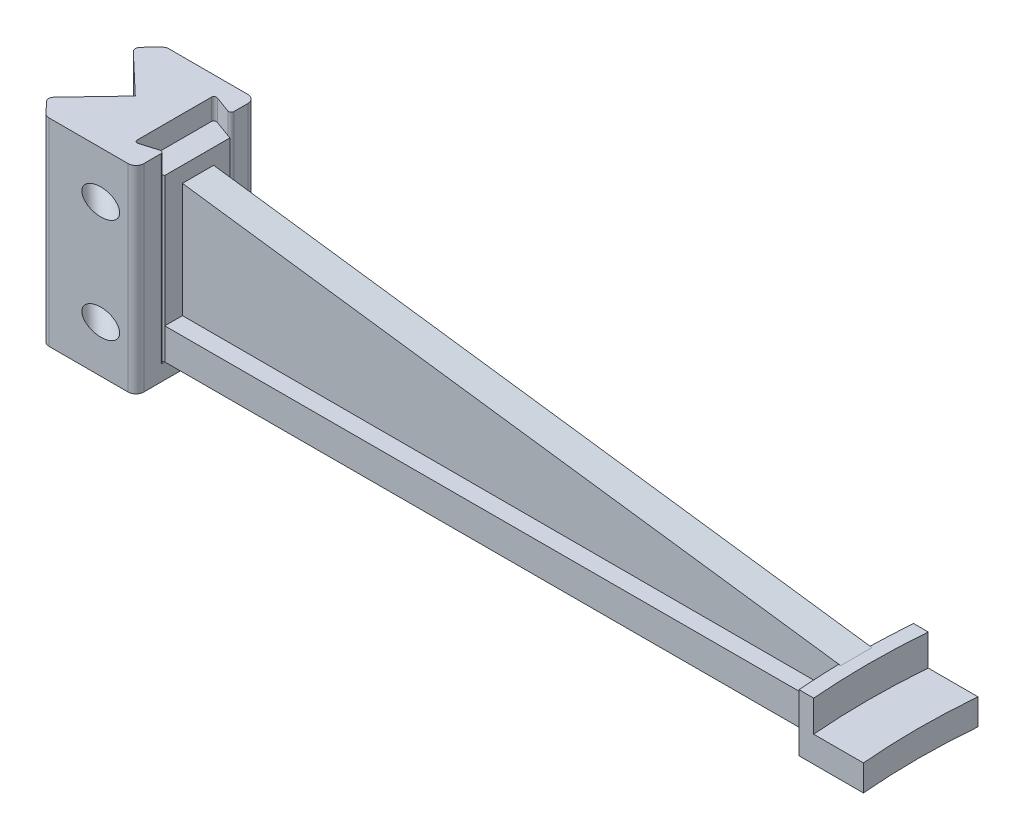
SolidWorks part; units mm, degrees
ref_plane "Front Plane" through (0, 0, 0) normal (0, 0, 1) x (1, 0, 0)
ref_plane "Top Plane" through (0, 0, 0) normal (0, 1, 0) x (1, 0, 0)
ref_plane "Right Plane" through (0, 0, 0) normal (1, 0, 0) x (0, 0, -1)
sketch "Sketch2" plane through (0, 0, 0) normal (0, 1, 0) x (1, 0, 0)
  line L0 (0, 0) -> (-276.0246, 0) construction
  line L1 (0, 0) -> (135.9511, 0) construction
  line L2 (-276.0246, 0) -> (-292.5966, 15.7434)
  line L3 (-292.5966, 15.7434) -> (-286.5108, 22.1496)
  line L4 (-286.5108, 22.1496) -> (-276.0246, 12.1877)
  line L5 (-276.0246, 12.1877) -> (-276.0246, 0)
  line L14 (0.8795, 22) -> (25.6062, 22)
  line L15 (0.8795, -22) -> (25.6062, -22)
  line L16 (25.6062, 22) -> (25.6062, -22) construction
  line L34 (-276.0246, 0) -> (-292.5966, -17.4443)
  line L49 (-292.5966, -17.4443) -> (-286.5108, -23.8504)
  line L50 (-286.5108, -23.8504) -> (-276.0246, -12.8123)
  line L51 (-276.0246, -12.8123) -> (-276.0246, 0)
  line L52 (-276.0246, 12.1877) -> (0.2836, 12.5)
  line L53 (-276.0246, -12.8123) -> (0.2836, -12.5)
  line L54 (0.2836, -12.5) -> (0.2836, 12.5) construction
  line L55 (-276.0246, 12.1877) -> (-276.0246, 24.2548) construction
  line L56 (-276.0246, -12.8123) -> (-276.0246, -19.1381)
  line L57 (-251.9246, 12.2149) -> (-260.9246, 15.4907)
  line L58 (-251.9246, 12.2149) -> (-251.9246, 22.1496)
  line L59 (-260.9246, 15.4907) -> (-260.9246, -15.4907)
  line L60 (-260.9246, -15.4907) -> (-251.9246, -12.7851)
  line L61 (-251.9246, -12.7851) -> (-251.9246, 12.2149)
  line L62 (-251.9246, 12.3214) -> (-261.0246, 15.6335)
  line L63 (-261.0246, 15.6335) -> (-261.0246, -15.6252)
  line L64 (-261.0246, -15.6252) -> (-251.9246, -12.8895)
  line L65 (-251.9246, -12.8895) -> (-251.9246, -23.8504)
  line L66 (-251.9246, -23.8504) -> (-286.5108, -23.8504)
  line L67 (-251.9246, 22.1496) -> (-286.5108, 22.1496)
  line L68 (-251.9246, -12.7851) -> (-251.9246, -12.8895)
  arc A0 (0.8795, 22) -> (0.8795, -22) centre (275.6, 0) ccw
  arc A1 (6.4978, 22) -> (6.4978, -22) centre (275.6, 0) ccw
  arc A2 (25.6062, 22) -> (25.6062, -22) centre (275.6, 0) ccw
  point P27 (-260.9246, 0)
  point P32 (5.6, 0)
  point P37 (0, 0)
  point P38 (192.5662, -22)
  point P39 (103.9258, -322.4114)
  point P40 (54.3973, 367.4504)
  dimension "D2" = 270
  dimension "D3" = 5.6
  dimension "D4" = 19.04
  dimension "D7" = 25
  dimension "D5" = 133.531
  dimension "D6" = 136.469
  dimension "D8" = 25
  dimension "D9" = 44
  dimension "D10" = 70
  dimension "D11" = 9
  dimension "D12" = 90
  dimension "D13" = 0.1
  dimension "D14" = 0.1
  dimension "D15" = 0.1
  dimension "D16" = 90
  dimension "D17" = 15
  dimension "D18" = 46
  dimension "D19" = 281.6246
extrude "Boss-Extrude2" add sketch "Sketch2" against normal blind 12 contours A0 L52 L59 L53 | A1 L14 A0 L15 | L59 L60 L53 | L57 L59 L52 | L53 L61 L52 L59 region at (-257.9246, 0, -13.3035) region at (-256.4246, 0, 0.2901) region at (-257.9246, 0, 13.6903) region at (-125.915, 0, 0.1426) region at (3.0963, 0, 0)
extrude "Boss-Extrude3" add sketch "Sketch2<5>" along normal blind 10 from surface contours A2 L14 A1 L15 region at (15.4307, 0, 0) starting at face at (-101.1356, -12, 0.057)
sketch "Sketch2<5>" plane through (0, 0, 0) normal (0, 1, 0) x (1, 0, 0) same geometry as "Sketch2"
extrude "Boss-Extrude4" add sketch "Sketch2<6>" along normal blind 22 from surface contours A1 L14 A0 L15 region at (3.0963, 0, 0) starting at face at (-97.3208, -12, 0.057)
sketch "Sketch2<6>" plane through (0, 0, 0) normal (0, 1, 0) x (1, 0, 0) same geometry as "Sketch2"
extrude "Boss-Extrude5" add sketch "Sketch2<7>" against normal blind 6 from surface separate body contours L5 L4 L3 L2 | L58 L67 L4 L52 L63 L62 | L63 L52 L5 L51 L53 | L50 L51 L34 L49 | L66 L65 L64 L63 L53 L50 | L68 L60 L59 L53 L63 L64 | L52 L63 L53 L59 | L53 L61 L52 L59 | L59 L60 L53 | L57 L59 L52 | L62 L63 L52 L59 L57 L58 | L66 L56 L50 region at (-282.9032, 0, -12.1717) region at (-282.9032, 0, 13.1665) region at (-268.5246, 0, 0.3038) region at (-267.2764, 0, -17.7114) region at (-267.126, 0, 18.8653) region at (-260.9273, 0, -13.9191) region at (-260.9746, 0, 0.2953) region at (-260.9745, 0, 12.8906) region at (-257.9246, 0, -13.3035) region at (-256.4246, 0, 0.2901) region at (-257.9246, 0, 13.6903) starting at face at (-97.3208, -12, 0.057)
sketch "Sketch2<7>" plane through (0, 0, 0) normal (0, 1, 0) x (1, 0, 0) same geometry as "Sketch2"
extrude "Boss-Extrude6" add sketch "Sketch2<8>" along normal blind 70 from surface contours L66 L65 L64 L63 L53 L50 | L50 L51 L34 L49 | L5 L4 L3 L2 | L58 L67 L4 L52 L63 L62 | L63 L52 L5 L51 L53 | L66 L56 L50 region at (-282.9032, 0, -12.1717) region at (-282.9032, 0, 13.1665) region at (-268.5246, 0, 0.3038) region at (-267.2764, 0, -17.7114) region at (-267.126, 0, 18.8653) starting at face at (-276.8698, -12, 0.7289)
sketch "Sketch2<8>" plane through (0, 0, 0) normal (0, 1, 0) x (1, 0, 0) same geometry as "Sketch2"
extrude "Boss-Extrude7" add sketch "Sketch2<9>" along normal blind 50 contours L53 L61 L52 L59 | L57 L59 L52 | L59 L60 L53 region at (-257.9246, 0, -13.3035) region at (-256.4246, 0, 0.2901) region at (-257.9246, 0, 13.6903)
sketch "Sketch2<9>" plane through (0, 0, 0) normal (0, 1, 0) x (1, 0, 0) same geometry as "Sketch2"
sketch "Sketch4" plane through (0, 0, 0) normal (0, 0, 1) x (1, 0, 0)
  line L5 (0.8795, 10) -> (-251.9246, 44)
  line L6 (-251.9246, 50) -> (-251.9246, 0) construction
  line L7 (-251.9246, 44) -> (-251.9246, 0)
  line L8 (-276.0246, 0) -> (0.2836, 0) construction
  line L9 (-251.9246, 0) -> (0.8795, 0)
  line L10 (0.8795, 0) -> (0.8795, 10)
  line L11 (0.8795, -12) -> (0.8795, 10) construction
  line L12 (0.8795, 10) -> (0, 10) construction
  point P15 (0, 0)
  point P16 (1.3309, 11.145)
  dimension "D1" = 44
extrude "Boss-Extrude17" add sketch "Sketch4" along normal blind 6 and the other way blind 6
sketch "Sketch5" plane through (-145.0852, 0, -137.8309) normal (-0.725, 0, -0.6887) x (-0.6887, 0, 0.725)
  line L0 (190.1118, -18) -> (190.1118, 58) construction
  line L1 (190.1118, 58) -> (210.1118, 58)
  line L2 (190.1118, 58) -> (190.1118, -18)
  line L3 (190.1118, -18) -> (210.1118, -18)
  line L4 (210.1118, 58) -> (210.1118, -18)
  line L5 (190.1118, 58) -> (210.1118, -18) construction
  line L6 (190.1118, -18) -> (210.1118, 58) construction
  line L7 (190.1118, -18) -> (214.1728, -18) construction
  line L8 (214.1728, 58) -> (190.1118, 58) construction
  line L10 (200.1118, 40) -> (200.1118, 0) construction
  circle A0 centre (200.1118, 40) radius 5
  circle A1 centre (200.1118, 0) radius 5
  circle A2 centre (200.1118, 0) radius 2.75
  circle A3 centre (200.1118, 40) radius 2.75
  point P0 (200.1118, 20)
  point P11 (200.1118, 20)
  dimension "D2" = 5.5
  dimension "D3" = 10
  dimension "D1" = 20
  dimension "D4" = 40
extrude "Cut-Extrude1" cut sketch "Sketch5" against normal through all from offset 8 contours A0 | A1 offset against normal yes
extrude "Cut-Extrude2" cut sketch "Sketch5<3>" against normal through all both and the other way through all contours A3 | A2 region at (-282.9121, 0, 7.25) region at (-282.9121, 40, 7.25)
sketch "Sketch5<3>" plane through (-145.0852, 0, -137.8309) normal (-0.725, 0, -0.6887) x (-0.6887, 0, 0.725) same geometry as "Sketch5"
mirror "Mirror1" about plane through (0, 0, 0) normal (0, 0, 1) of "Cut-Extrude2", "Cut-Extrude1"
fillet "Fillet1" radius 1 4 edges at (-251.9246, 23, 12.8895) (-251.9246, 23, -12.3214) (-261.0246, 23, 15.6252) (-261.0246, 23, -15.6335)
fillet "Fillet2" radius 1 2 edges at (-260.9246, 19, 15.4907) (-260.9246, 19, -15.4907)
fillet "Fillet3" radius 3 4 edges at (-286.5108, 20, -22.1496) (-286.5108, 20, 23.8504) (-251.9246, 20, -22.1496) (-251.9246, 20, 23.8504)
fillet "Fillet4" radius 2 2 edges at (-292.5966, 20, -15.7434) (-292.5966, 20, 17.4443)
